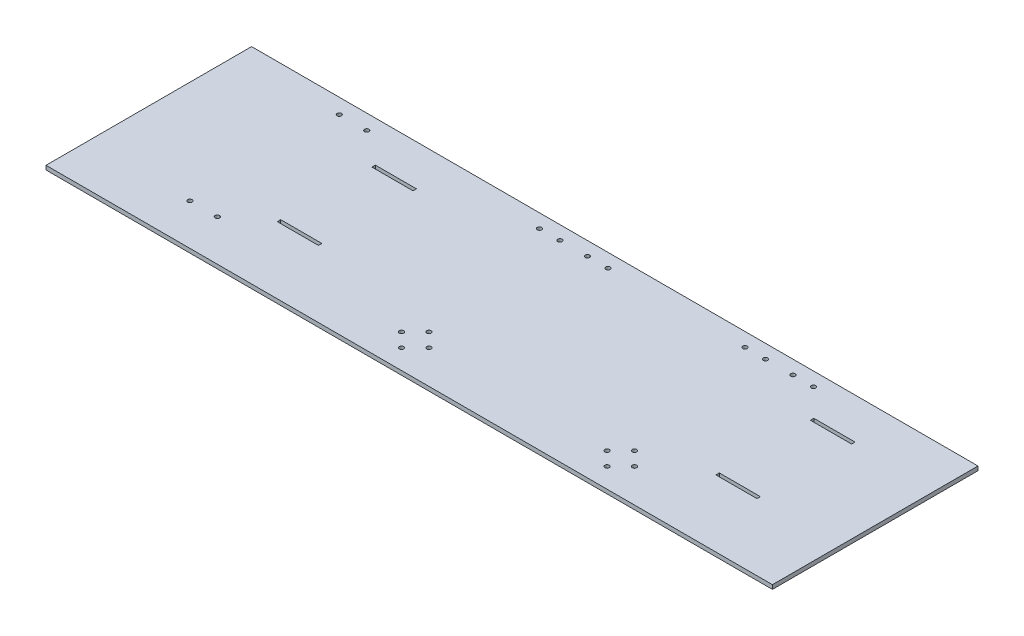
SolidWorks part; units mm, degrees
ref_plane "前视基准面" through (0, 0, 0) normal (0, 0, 1) x (1, 0, 0)
ref_plane "上视基准面" through (0, 0, 0) normal (0, 1, 0) x (1, 0, 0)
ref_plane "右视基准面" through (0, 0, 0) normal (1, 0, 0) x (0, 0, -1)
other "Configuration Table"
sketch "草图1" plane through (0, 0, 0) normal (0, 1, 0) x (1, 0, 0)
  line L0 (-223.1325, 65.7911) -> (246.8675, 65.7911) construction
  line L1 (-223.1325, 96.7911) -> (246.8675, 96.7911)
  line L2 (-223.1325, 96.7911) -> (-223.1325, -53.2089) construction
  line L3 (-223.1325, -53.2089) -> (246.8675, -53.2089)
  line L4 (246.8675, 96.7911) -> (246.8675, -53.2089)
  line L5 (-223.1325, -3.2089) -> (246.8675, -3.2089) construction
  line L6 (11.8675, 96.7911) -> (11.8675, -53.2089) construction
  line L7 (-163.1325, -1.9589) -> (-133.1325, -1.9589)
  line L8 (-163.1325, -1.9589) -> (-163.1325, -4.4589)
  line L9 (-163.1325, -4.4589) -> (-133.1325, -4.4589)
  line L10 (-133.1325, -1.9589) -> (-133.1325, -4.4589)
  line L11 (186.8675, -1.9589) -> (186.8675, -4.4589)
  line L12 (156.8675, -1.9589) -> (156.8675, -4.4589)
  line L13 (186.8675, -4.4589) -> (156.8675, -4.4589)
  line L14 (186.8675, -1.9589) -> (156.8675, -1.9589)
  line L15 (-209.769, 65.7911) -> (-209.769, -3.2089) construction
  line L16 (-209.769, 31.2911) -> (246.8675, 31.2911) construction
  line L17 (156.8675, 64.5411) -> (156.8675, 67.0411)
  line L18 (186.8675, 67.0411) -> (156.8675, 67.0411)
  line L19 (186.8675, 64.5411) -> (186.8675, 67.0411)
  line L20 (186.8675, 64.5411) -> (156.8675, 64.5411)
  line L21 (-163.1325, 67.0411) -> (-133.1325, 67.0411)
  line L22 (-133.1325, 64.5411) -> (-133.1325, 67.0411)
  line L23 (-163.1325, 64.5411) -> (-133.1325, 64.5411)
  line L24 (-163.1325, 64.5411) -> (-163.1325, 67.0411)
  line L25 (-148.1325, -4.4589) -> (-148.1325, -53.2089) construction
  line L26 (-223.1325, -53.2089) -> (-283.1325, -53.2089)
  line L28 (-223.1325, 96.7911) -> (-283.1325, 96.7911)
  line L29 (-283.1325, -53.2089) -> (-283.1325, 96.7911)
  line L30 (171.8675, -4.4589) -> (171.8675, -53.2089) construction
  line L31 (-188.1325, -23.2089) -> (-208.1325, -23.2089) construction
  line L32 (-148.1325, -28.8339) -> (11.8675, -28.8339) construction
  line L33 (171.8675, -28.8339) -> (11.8675, -28.8339) construction
  line L34 (-38.1325, -28.8339) -> (-38.1325, 96.7911) construction
  line L35 (111.8675, -28.8339) -> (111.8675, 96.7911) construction
  line L36 (-63.1325, 86.7911) -> (-48.1325, 86.7911) construction
  line L37 (86.8675, 86.7911) -> (101.8675, 86.7911) construction
  circle A0 centre (-208.1325, -23.2089) radius 1.6
  circle A1 centre (-188.1325, -23.2089) radius 1.6
  circle A2 centre (-208.1325, 85.7911) radius 1.6
  circle A3 centre (-188.1325, 85.7911) radius 1.6
  circle A4 centre (-38.1325, -28.8339) radius 10 construction
  circle A5 centre (111.8675, -28.8339) radius 10 construction
  circle A6 centre (-48.1325, -28.8339) radius 1.6
  circle A7 centre (-38.1325, -38.8339) radius 1.6
  circle A8 centre (-28.1325, -28.8339) radius 1.6
  circle A9 centre (-38.1325, -18.8339) radius 1.6
  circle A10 centre (101.8675, -28.8339) radius 1.6
  circle A11 centre (111.8675, -18.8339) radius 1.6
  circle A12 centre (121.8675, -28.8339) radius 1.6
  circle A13 centre (111.8675, -38.8339) radius 1.6
  circle A14 centre (-63.1325, 86.7911) radius 1.6
  circle A15 centre (-48.1325, 86.7911) radius 1.6
  circle A16 centre (-28.1325, 86.7911) radius 1.6
  circle A17 centre (-13.1325, 86.7911) radius 1.6
  circle A20 centre (86.8675, 86.7911) radius 1.6
  circle A21 centre (101.8675, 86.7911) radius 1.6
  circle A22 centre (136.8675, 86.7911) radius 1.6
  circle A23 centre (121.8675, 86.7911) radius 1.6
  point P12 (-163.1325, -3.2089)
  dimension "D9" = 3.2
  dimension "D13" = 150
  dimension "D15" = 20
  dimension "D16" = 3.2
  dimension "D17" = 3.2
  dimension "D21" = 3.2
  dimension "D1" = 470
  dimension "D2" = 150
  dimension "D3" = 69
  dimension "D4" = 50
  dimension "D5" = 60
  dimension "D6" = 2.5
  dimension "D7" = 30
  dimension "D8" = 60
  dimension "D10" = 20
  dimension "D11" = 20
  dimension "D12" = 15
  dimension "D14" = 50
  dimension "D18" = 15
  dimension "D19" = 10
  dimension "D20" = 10
  dimension "D22" = 10
  dimension "D23" = 15
  dimension "D24" = 10
extrude "凸台-拉伸1" add sketch "草图1" along normal blind 3
